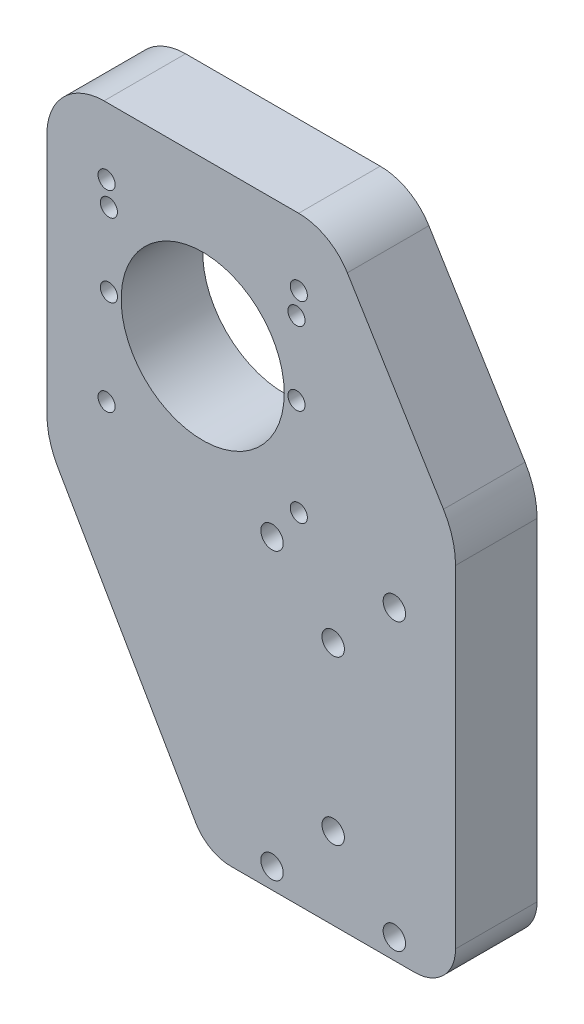
SolidWorks part; units mm, degrees
ref_plane "Front Plane" through (0, 0, 0) normal (0, 0, 1) x (1, 0, 0)
ref_plane "Top Plane" through (0, 0, 0) normal (0, 1, 0) x (1, 0, 0)
ref_plane "Right Plane" through (0, 0, 0) normal (1, 0, 0) x (0, 0, -1)
sketch "Sketch1" plane through (0, 0, 0) normal (0, 0, 1) x (1, 0, 0)
  line L0 (-130, 510) -> (13.8884, 510) construction
  line L1 (-170.2, 540.8246) -> (-129.3094, 470)
  line L2 (-116.2253, 607) -> (-90, 564.2553)
  line L15 (-90, 473) -> (-90, 564.2553)
  line L16 (-90, 473) -> (-90, 547) construction
  line L24 (-170.2, 540.8246) -> (-170.2, 607)
  line L25 (-170.2, 607) -> (-116.2253, 607)
  line L183 (-129.3094, 470) -> (-93, 470)
  arc A1 (-113.8, 602.2) -> (-116.8, 605.2) centre (-116.8, 602.2) ccw construction
  arc A13 (-90, 473) -> (-93, 470) centre (-93, 473) cw
extrude "Boss-Extrude1" add sketch "Sketch1" along normal blind 20
fillet "Fillet1" radius 10 3 edges at (-129.3094, 470, 10) (-170.2, 540.8246, 10) (-90, 564.2553, 10)
sketch "Sketch2" plane through (0, 0, 20) normal (0, 0, 1) x (1, 0, 0)
  circle A0 centre (-142, 577) radius 20
  dimension "D1" = 40
extrude "Cut-Extrude1" cut sketch "Sketch2" against normal blind 20
hole_wizard "Tap Drill for M5 Tap1" positions "Sketch5" profile "Sketch6" hole size "M5" standard "ISO" end condition through all
sketch "Sketch5" plane through (0, 0, 0) normal (0, 0, -1) x (-1, 0, 0)
  line L1 (119, 595) -> (119, 577)
  line L2 (119, 595) -> (165, 595)
  line L3 (165, 595) -> (165, 577)
  line L4 (119, 577) -> (165, 577)
  circle A1 centre (119, 595) radius 2.1
  point P2 (119, 595)
  point P4 (119, 577)
  point P6 (165, 577)
  point P8 (165, 595)
  dimension "D1" = 18
  dimension "D2" = 46
  dimension "D3" = 46
  dimension "D4" = 18
sketch "Sketch6" plane through (-119, 595, 0) normal (1, 0, 0) x (0, 1, 0)
  line L0 (0, 0) -> (0, 20)
  line L1 (0, 20) -> (2.1, 20)
  line L2 (2.1, 20) -> (2.1, 0)
  line L5 (2.1, 0) -> (0, 0)
  line L11 (0, -6.35) -> (0, 107.95) construction
  dimension "Thru Hole Dia." = 4.2
  dimension "Thru Hole Depth" = 20
hole_wizard "M5 Clearance Hole1" positions "Sketch7" profile "Sketch8" hole size "M5" standard "ISO" end condition through all
sketch "Sketch7" plane through (0, 0, 20) normal (0, 0, 1) x (1, 0, 0)
  point P0 (-95, 545)
  point P2 (-125, 545)
  point P4 (-125, 475)
  point P6 (-95, 475)
  point P8 (-110, 490)
  point P10 (-110, 530)
sketch "Sketch8" plane through (-95, 545, 20) normal (1, 0, 0) x (0, -1, 0)
  line L0 (0, 0) -> (0, 20)
  line L1 (0, 20) -> (2.75, 20)
  line L2 (2.75, 20) -> (2.75, 0)
  line L5 (2.75, 0) -> (0, 0)
  line L11 (0, -6.35) -> (0, 107.95) construction
  dimension "Thru Hole Dia." = 5.5
  dimension "Thru Hole Depth" = 20
hole_wizard "Tap Drill for M5 Tap2" positions "Sketch9" profile "Sketch10" hole size "M5" standard "ISO" end condition through all
sketch "Sketch9" plane through (0, 0, 20) normal (0, 0, 1) x (1, 0, 0)
  point P0 (-165.57, 553.43)
  point P2 (-165.57, 600.57)
  point P4 (-118.43, 553.43)
  point P6 (-118.43, 600.57)
sketch "Sketch10" plane through (-165.57, 553.43, 20) normal (1, 0, 0) x (0, -1, 0)
  line L0 (0, 0) -> (0, 20)
  line L1 (0, 20) -> (2.1, 20)
  line L2 (2.1, 20) -> (2.1, 0)
  line L5 (2.1, 0) -> (0, 0)
  line L11 (0, -6.35) -> (0, 107.95) construction
  dimension "Thru Hole Dia." = 4.2
  dimension "Thru Hole Depth" = 20
fillet "Fillet2" radius 4 2 edges at (-116.2253, 607, 10) (-170.2, 607, 10)
sketch "Sketch11" plane through (0, 0, 20) normal (0, 0, 1) x (1, 0, 0)
  line L0 (-82.9528, 571.8912) -> (-106.531, 610.3213)
  line L1 (-118.464, 617) -> (-166.2, 617)
  line L2 (-180.2, 603) -> (-180.2, 543.5041)
  line L3 (-177.5205, 533.5041) -> (-143.7432, 475)
  line L5 (-80, 480) -> (-80, 561.4321)
  line L6 (-91.4764, 566.6616) -> (-115.0546, 605.0918)
  line L7 (-118.464, 607) -> (-166.2, 607)
  line L8 (-170.2, 603) -> (-170.2, 543.5041)
  line L9 (-168.8603, 538.5041) -> (-132.1962, 475)
  line L10 (-123.5359, 470) -> (-93, 470)
  line L11 (-90, 473) -> (-90, 561.4321)
  line L12 (-91.4764, 566.6616) -> (-115.0546, 605.0918)
  line L13 (-118.464, 607) -> (-166.2, 607)
  line L14 (-170.2, 603) -> (-170.2, 543.5041)
  line L15 (-168.8603, 538.5041) -> (-132.1962, 475)
  line L16 (-135.0829, 470) -> (-90, 470)
  line L17 (-90, 473) -> (-90, 561.4321)
  line L18 (-123.5359, 470) -> (-93, 470) construction
  line L19 (-80, 473) -> (-80, 561.4321) construction
  line L20 (-123.5359, 460) -> (-93, 460) construction
  line L21 (-177.5205, 533.5041) -> (-140.8564, 470) construction
  arc A0 (-106.531, 610.3213) -> (-118.464, 617) centre (-118.464, 603) ccw
  arc A1 (-166.2, 617) -> (-180.2, 603) centre (-166.2, 603) ccw
  arc A2 (-180.2, 543.5041) -> (-177.5205, 533.5041) centre (-160.2, 543.5041) ccw
  arc A5 (-80, 561.4321) -> (-82.9528, 571.8912) centre (-100, 561.4321) ccw
  arc A6 (-115.0546, 605.0918) -> (-118.464, 607) centre (-118.464, 603) ccw
  arc A7 (-166.2, 607) -> (-170.2, 603) centre (-166.2, 603) ccw
  arc A8 (-170.2, 543.5041) -> (-168.8603, 538.5041) centre (-160.2, 543.5041) ccw
  arc A9 (-132.1962, 475) -> (-123.5359, 470) centre (-123.5359, 480) ccw
  arc A10 (-93, 470) -> (-90, 473) centre (-93, 473) ccw
  arc A11 (-90, 561.4321) -> (-91.4764, 566.6616) centre (-100, 561.4321) ccw
  arc A12 (-115.0546, 605.0918) -> (-118.464, 607) centre (-118.464, 603) ccw
  arc A13 (-166.2, 607) -> (-170.2, 603) centre (-166.2, 603) ccw
  arc A14 (-170.2, 543.5041) -> (-168.8603, 538.5041) centre (-160.2, 543.5041) ccw
  arc A15 (-132.1962, 475) -> (-123.5359, 470) centre (-123.5359, 480) ccw
  arc A16 (-93, 470) -> (-90, 473) centre (-93, 473) ccw
  arc A17 (-90, 561.4321) -> (-91.4764, 566.6616) centre (-100, 561.4321) ccw
  arc A18 (-93, 460) -> (-80, 473) centre (-93, 473) ccw construction
  arc A19 (-140.8564, 470) -> (-123.5359, 460) centre (-123.5359, 480) ccw construction
  arc A20 (-143.7432, 475) -> (-135.0829, 470) centre (-135.0829, 480) ccw
  arc A21 (-90, 470) -> (-80, 480) centre (-90, 480) ccw
  line M41 (-91.4764, 566.6616) -> (-115.0546, 605.0918)
  arc M42 (-115.0546, 605.0918) -> (-118.464, 607) centre (-118.464, 603) ccw
  line M43 (-118.464, 607) -> (-166.2, 607)
  arc M44 (-166.2, 607) -> (-170.2, 603) centre (-166.2, 603) ccw
  line M45 (-170.2, 603) -> (-170.2, 543.5041)
  arc M46 (-170.2, 543.5041) -> (-168.8603, 538.5041) centre (-160.2, 543.5041) ccw
  line M47 (-168.8603, 538.5041) -> (-132.1962, 475)
  arc M48 (-132.1962, 475) -> (-123.5359, 470) centre (-123.5359, 480) ccw
  arc M50 (-93, 470) -> (-90, 473) centre (-93, 473) ccw
  line M51 (-90, 473) -> (-90, 561.4321)
  arc M52 (-90, 561.4321) -> (-91.4764, 566.6616) centre (-100, 561.4321) ccw
  dimension "D3" = 10
  dimension "D1" = 0
  dimension "D2" = 10
extrude "Boss-Extrude2" add sketch "Sketch11" against normal up to surface (20 mm away) contours L16 A21 L5 A5 L0 A0 L1 A1 L2 A2 L3 A20 M48 M47 M46 M45 M44 M43 M42 M41 M52 M51 M50 region at (-82.4644, 566.3827, 20) up to face at (-163.47, 553.43, 0)
